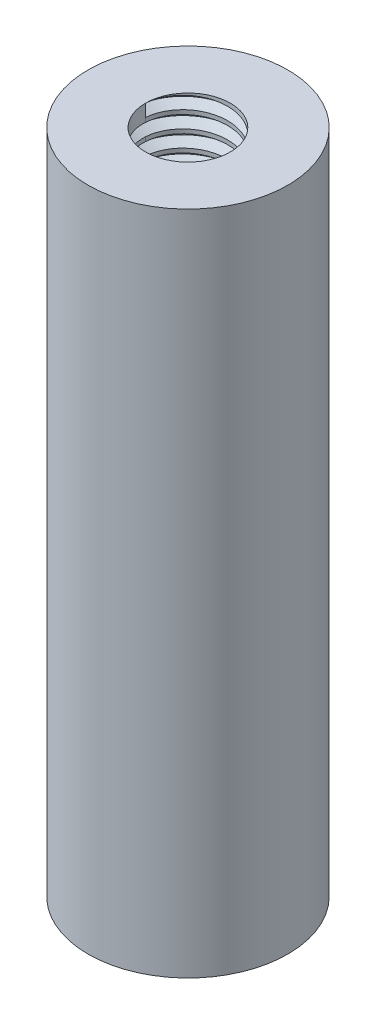
SolidWorks part; units mm, degrees
material "6061-T6 (SS)"
ref_plane "Front Plane" through (0, 0, 0) normal (0, 0, 1) x (1, 0, 0)
ref_plane "Top Plane" through (0, 0, 0) normal (0, 1, 0) x (1, 0, 0)
ref_plane "Right Plane" through (0, 0, 0) normal (1, 0, 0) x (0, 0, -1)
other "Bounding Box"
ref_plane "Default Plane" through (13.8565, 3.175, 6.7999) normal (0, -1, 0) x (-1, 0, 0)
sketch "Sketch1" plane through (0, 0, 0) normal (0, 1, 0) x (1, 0, 0)
  circle A0 centre (0, 0) radius 4.7625
  circle A1 centre (0, 0) radius 2.0193
  dimension "D1" = 9.525
  dimension "D2" = 4.0386
extrude "Boss-Extrude1" add sketch "Sketch1" along normal mid plane 31.75
thread "Thread1" pitch 0.7937 method cut profile "Thread Profile2" start angle 0, offset 0, length 9.525, pitch 0.7937, diameter 4.0386
ref_plane "Plane2" through (-2.0193, 15.875, 0) normal (0, 0, 1) x (-1, 0, 0)
sketch "Thread Profile2" plane through (-2.0193, 15.875, 0) normal (0, 0, 1) x (-1, 0, 0)
  line L0 (0, 0) -> (0, 0.7937) construction
  line L1 (0, 0) -> (0.4296, 0.248)
  line L2 (0.4296, 0.248) -> (0.4296, 0.3473)
  line L3 (0.4296, 0.3473) -> (0, 0.5953)
  line L4 (0.4296, 0.2977) -> (0, 0.2977) construction
  line L11 (0, 0) -> (0, 0.5953)
  point P2 (0, 0)
  dimension "Pitch" = 0.7937
  dimension "Profile_Angle" = 60
  dimension "Profile_Land" = 0.0992
  dimension "Profile_Height" = 0.4296
mirror "Mirror3" about plane through (0, 0, 0) normal (0, 1, 0) of "Thread1"
